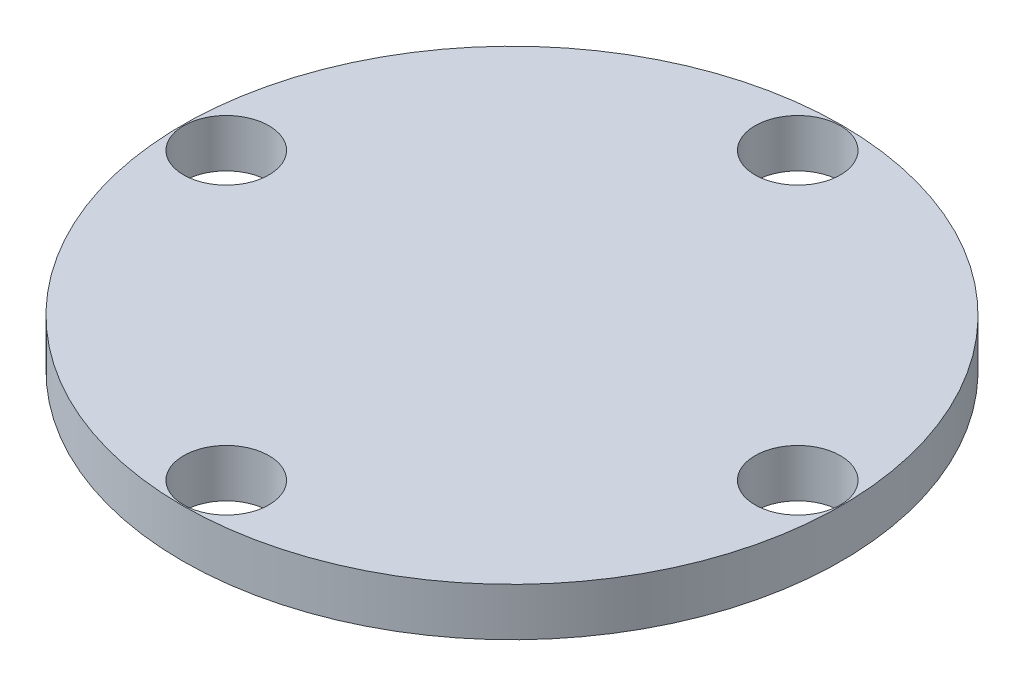
SolidWorks part; units mm, degrees
material "Custom Plastic"
ref_plane "Front Plane" through (0, 0, 0) normal (0, 0, 1) x (1, 0, 0)
ref_plane "Top Plane" through (0, 0, 0) normal (0, 1, 0) x (1, 0, 0)
ref_plane "Right Plane" through (0, 0, 0) normal (1, 0, 0) x (0, 0, -1)
sketch "Sketch1" plane through (0, 0, 0) normal (0, 1, 0) x (1, 0, 0)
  circle A0 centre (0, 0) radius 10.9855
  dimension "D1" = 21.971
extrude "Boss-Extrude1" add sketch "Sketch1" along normal blind 1.6002
sketch "Sketch2" plane through (0, 1.6002, 0) normal (0, 1, 0) x (1, 0, 0)
  circle A0 centre (-9.525, 0) radius 1.4224
  dimension "D1" = 2.8448
  dimension "D2" = 9.525
ref_axis "Axis1" through (0, 1.6002, 0) along (0, -1, 0)
extrude "Cut-Extrude1" cut sketch "Sketch2" against normal blind 1.6002
pattern_circular "CirPattern1" count 4 over 360 about axis through (0, 1.6002, 0) along (0, -1, 0) of "Cut-Extrude1"
